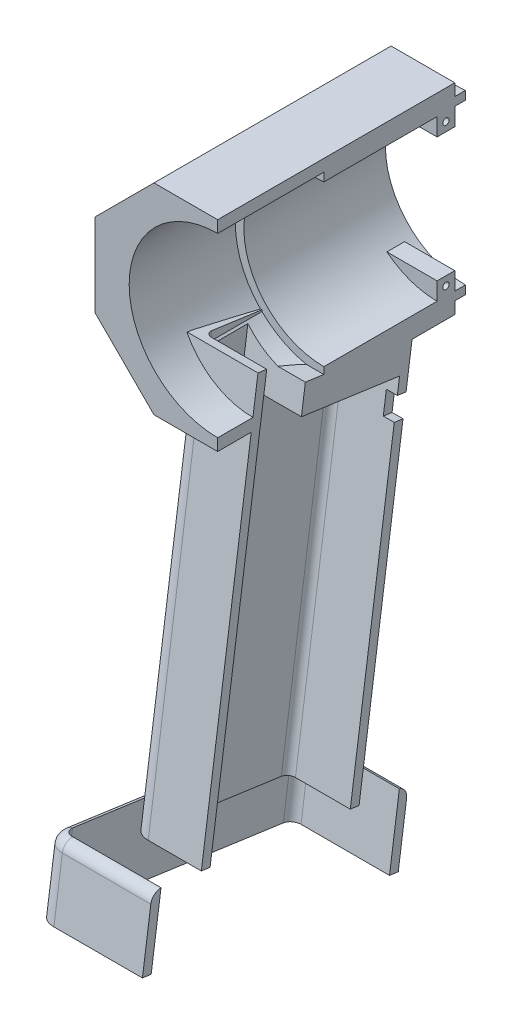
SolidWorks part; units mm, degrees
ref_plane "Ön Düzlem" through (0, 0, 0) normal (0, 0, 1) x (1, 0, 0)
ref_plane "Üst Düzlem" through (0, 0, 0) normal (0, 1, 0) x (1, 0, 0)
ref_plane "Sağ Düzlem" through (0, 0, 0) normal (1, 0, 0) x (0, 0, -1)
sketch "Çizim1" plane through (0, 0, 0) normal (0, 0, 1) x (1, 0, 0)
  line L0 (0, 0) -> (-18, 0)
  line L1 (-18, 0) -> (-34.617, 16.617)
  line L2 (-34.617, 16.617) -> (-34.617, 40.117)
  line L3 (-34.617, 40.117) -> (-18, 56.734)
  line L4 (-18, 56.734) -> (0, 56.734)
  line L5 (0, 56.734) -> (0, 0)
  dimension "D1" = 18
  dimension "D2" = 23.5
  dimension "D3" = 135
extrude "Yükseklik-Ekstrüzyon1" add sketch "Çizim1" along normal blind 67
sketch "Çizim2" plane through (0, 0, 67) normal (0, 0, 1) x (1, 0, 0)
  line L0 (0, 0) -> (0, 56.734) construction
  circle A0 centre (0, 28.367) radius 25
  dimension "D1" = 50
extrude "Kes-Ekstrüzyon1" cut sketch "Çizim2" against normal blind 70
ref_plane "Düzlem1" through (0, 0, 37) normal (0, 0, 1) x (1, 0, 0)
sketch "Çizim5" plane through (0, 0, 37) normal (0, 0, 1) x (1, 0, 0)
  line L0 (0, 53.367) -> (0, 50.967)
  line L1 (0, 3.367) -> (0, 5.767)
  line L7 (0, 0) -> (0, 3.367)
  line L8 (0, 53.367) -> (0, 56.734)
  line L9 (0, 56.734) -> (-18, 56.734)
  line L10 (-18, 56.734) -> (-34.617, 40.117)
  line L11 (-34.617, 40.117) -> (-34.617, 16.617)
  line L12 (-34.617, 16.617) -> (-18, 0)
  line L13 (-18, 0) -> (0, 0)
  line L14 (0, 0) -> (0, 3.367)
  line L15 (0, 53.367) -> (0, 56.734)
  line L16 (0, 56.734) -> (-18, 56.734)
  line L17 (-18, 56.734) -> (-34.617, 40.117)
  line L18 (-34.617, 40.117) -> (-34.617, 16.617)
  line L19 (-34.617, 16.617) -> (-18, 0)
  line L20 (-18, 0) -> (0, 0)
  circle A1 centre (0, 28.367) radius 22.6
  arc A2 (0, 53.367) -> (0, 3.367) centre (0, 28.367) ccw
  arc A3 (0, 53.367) -> (0, 3.367) centre (0, 28.367) ccw
  dimension "D2" = 45.2
  dimension "D1" = 0
extrude "Yükseklik-Ekstrüzyon2" add sketch "Çizim5" against normal blind 40 contours L0 A3 L1 A1
sketch "Çizim7" plane through (0, 0, 0) normal (1, 0, 0) x (0, 0, -1)
  line L2 (-67, 0) -> (0.5017, -9.4868) construction
  line L3 (-67, 0) -> (0, 0) construction
  point P2 (0, 0)
  dimension "D1" = 8
sketch "Çizim11" plane through (0, 0, 37) normal (0, 0, 1) x (1, 0, 0)
  circle A0 centre (0, 28.367) radius 22.5
ref_plane "Düzlem3" through (0, 0, 27) normal (0, 0, 1) x (1, 0, 0)
sketch "Çizim15" plane through (0, 0, 0) normal (1, 0, 0) x (0, 0, -1)
  line L1 (0, 5.767) -> (-5, 5.767)
  line L2 (0, 5.767) -> (0, 10.767)
  line L3 (0, 10.767) -> (-5, 10.767)
  line L4 (-5, 5.767) -> (-5, 10.767)
  line L5 (0, 50.967) -> (-5, 50.967)
  line L6 (0, 50.967) -> (0, 45.967)
  line L7 (0, 45.967) -> (-5, 45.967)
  line L8 (-5, 50.967) -> (-5, 45.967)
  circle A0 centre (-2.5, 8.267) radius 0.9
  circle A1 centre (-2.5, 48.467) radius 0.9
  point P12 (0, 8.267)
  point P13 (-2.5, 10.767)
  point P16 (0, 48.467)
  point P17 (-2.5, 45.967)
  dimension "D2" = 1.8
  dimension "D1" = 5
ref_plane "Düzlem4" through (0, -9.2339, 1.2977) normal (0, -0.9903, 0.1392) x (0, -0.1392, -0.9903)
sketch "Çizim21" plane through (0, -9.2339, 1.2977) normal (0, -0.9903, 0.1392) x (0, -0.1392, -0.9903)
  line L0 (-66.348, 0) -> (1.8172, 0) construction
  line L2 (-56.9532, 0) -> (-56.9532, -20)
  line L3 (-56.9532, -20) -> (-11.9532, -20)
  line L4 (-11.9532, 0) -> (-11.9532, -20)
  line L5 (-54.4532, 0) -> (-54.4532, -17.5)
  line L6 (-54.4532, -17.5) -> (-14.4532, -17.5)
  line L7 (-14.4532, 0) -> (-14.4532, -17.5)
  line L8 (-56.9532, 0) -> (-54.4532, 0)
  line L9 (-14.4532, 0) -> (-11.9532, 0)
  dimension "D1" = 45
  dimension "D2" = 20
  dimension "D3" = 2.5
extrude "Yükseklik-Ekstrüzyon7" add sketch "Çizim21" along normal blind 100 and the other way blind 15 separate body
extrude "Yükseklik-Ekstrüzyon8" add sketch "Çizim15" against normal blind 16
extrude "Kes-Ekstrüzyon17" cut sketch "Çizim11" against normal blind 33
sketch "Çizim24" plane through (0, -9.2339, 1.2977) normal (0, -0.9903, 0.1392) x (0, -0.1392, -0.9903)
  line L1 (-54.4532, 0) -> (-42.4532, 0)
  line L2 (-54.4532, 0) -> (-54.4532, -17)
  line L3 (-54.4532, -17) -> (-42.4532, -17)
  line L4 (-42.4532, 0) -> (-42.4532, -17)
  dimension "D1" = 17
  dimension "D2" = 12
extrude "Kes-Ekstrüzyon18" cut sketch "Çizim24" against normal blind 20
sketch "Çizim29" plane through (0, -9.2339, 1.2977) normal (0, -0.9903, 0.1392) x (0, -0.1392, -0.9903)
  line L0 (-14.4532, -17.5) -> (-54.4532, -17.5) construction
  line L1 (-42.4532, 0) -> (-14.4532, 0)
  line L2 (-42.4532, 0) -> (-42.4532, -17.5)
  line L3 (-42.4532, -17.5) -> (-14.4532, -17.5)
  line L4 (-14.4532, 0) -> (-14.4532, -17.5)
  line L5 (-14.4532, 0) -> (-14.4532, -17.5) construction
extrude "Yükseklik-Ekstrüzyon12" add sketch "Çizim29" against normal blind 8
sketch "Çizim34" plane through (0, 1.6636, 11.8368) normal (0, -0.1392, -0.9903) x (-1, 0, 0)
  line L0 (0, -1.6799) -> (0, -109.3246) construction
  line L1 (0, -20.0246) -> (3.1, -20.0246)
  line L2 (0, -20.0246) -> (0, -13.8246)
  line L3 (0, -13.8246) -> (3.1, -13.8246)
  line L4 (3.1, -20.0246) -> (3.1, -13.8246)
  dimension "D1" = 3.1
  dimension "D2" = 6.2
  dimension "D3" = 4.5
extrude "Kes-Ekstrüzyon20" cut sketch "Çizim34" against normal blind 3
ref_plane "Düzlem5" through (-1.5, 0, 0) normal (1, 0, 0) x (0, 0, -1)
sketch "Çizim44" plane through (0, 0, 37) normal (0, 0, 1) x (1, 0, 0)
  circle A0 centre (0, 28.367) radius 22.6
extrude "Kes-Ekstrüzyon25" cut sketch "Çizim44" against normal blind 30
fillet "Radyus4" radius 5 2 edges at (-20, -52.2986, 19.4207) (-20, -49.1672, 64.4229)
fillet "Radyus5" radius 2 2 edges at (-17.5, -50.3411, 62.0633) (-17.5, -56.7358, 22.5689)
sketch "Çizim45" plane through (0, -108.2607, 15.215) normal (0, -0.9903, 0.1392) x (1, 0, 0)
  line L0 (-17.5, 16.4532) -> (-17.5, 52.4532) construction
  line L1 (0, -2.0468) -> (-25, -2.0468)
  line L3 (0, 70.9532) -> (-25, 70.9532)
  line L4 (-30, 2.9532) -> (-30, 65.9532)
  line L5 (0, 0.4532) -> (-25, 0.4532)
  line L6 (0, -2.0468) -> (0, 70.9532) construction
  line L7 (0, 66.348) -> (0, -1.8172) construction
  line L8 (-27.5, 2.9532) -> (-27.5, 65.9532)
  line L9 (0, 68.4532) -> (-25, 68.4532)
  line L10 (0, -2.0468) -> (0, 0.4532)
  line L11 (0, 68.4532) -> (0, 70.9532)
  arc A0 (-25, 70.9532) -> (-30, 65.9532) centre (-25, 65.9532) ccw
  arc A1 (-25, -2.0468) -> (-30, 2.9532) centre (-25, 2.9532) cw
  arc A2 (-25, 0.4532) -> (-27.5, 2.9532) centre (-25, 2.9532) cw
  arc A3 (-25, 68.4532) -> (-27.5, 65.9532) centre (-25, 65.9532) ccw
  point P6 (-17.5, 34.4532)
  point P7 (-30, 34.4532)
  point P13 (-30, 70.9532)
  point P16 (-30, -2.0468)
  dimension "D3" = 5
  dimension "D1" = 30
  dimension "D2" = 73
  dimension "D4" = 2.5
extrude "Yükseklik-Ekstrüzyon16" add sketch "Çizim45" along normal blind 20 separate body
ref_plane "Düzlem6" through (0, 0, 67) normal (0, 0, 1) x (1, 0, 0)
fillet "Radyus7" radius 3 2 edges at (-12.5, -108.5455, 13.1881) (-12.5, -98.3859, 85.4777)
sketch "Çizim53" plane through (0, 0, 0) normal (1, 0, 0) x (0, 0, -1)
  circle A0 centre (-32, 1) radius 0.9
  circle A1 centre (-32, 53.8) radius 0.9
  dimension "D1" = 1.8
  dimension "D2" = 32
  dimension "D3" = 1
  dimension "D4" = 53.8
sketch "Çizim54" plane through (-17.5, 0, 0) normal (1, 0, 0) x (0, 0, -1)
  circle A0 centre (-37, -80) radius 4
  circle A1 centre (-37, -80) radius 3.1
  dimension "D1" = 8
  dimension "D2" = 37
  dimension "D3" = 80
  dimension "D4" = 6.2
